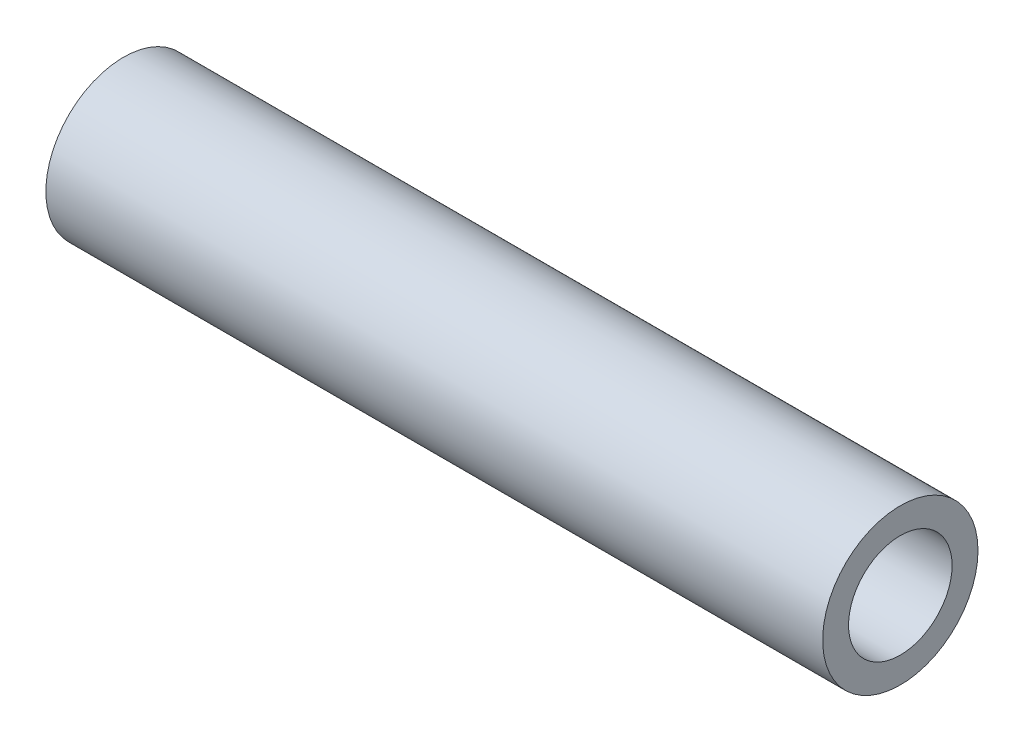
SolidWorks part; units mm, degrees
material "炭素鋼(普通)"
ref_plane "HOR" through (0, 0, 0) normal (0, 0, 1) x (1, 0, 0)
ref_plane "VERT" through (0, 0, 0) normal (0, 1, 0) x (1, 0, 0)
ref_plane "CTR" through (0, 0, 0) normal (1, 0, 0) x (0, 0, -1)
ref_axis "A_X" through (88.99, 0, 0) along (-1, 0, 0)
ref_axis "A_Y" through (0, 55, 0) along (0, -1, 0)
ref_axis "A_Z" through (0, 0, 55) along (0, 0, -1)
sketch3d "PNT_CG"
  point P0 (0, 0, 0)
sketch "Sketch1" plane through (0, 0, 0) normal (1, 0, 0) x (0, 0, -1)
  circle A0 centre (0, 0) radius 30
  dimension "D1" = 60
extrude "Boss-Extrude1" add sketch "Sketch1" along normal blind 300
sketch "Sketch2" plane through (300, 0, 0) normal (1, 0, 0) x (0, 0, -1)
  circle A0 centre (0, 0) radius 20
  dimension "D1" = 40
extrude "Cut-Extrude1" cut sketch "Sketch2" against normal blind 300
